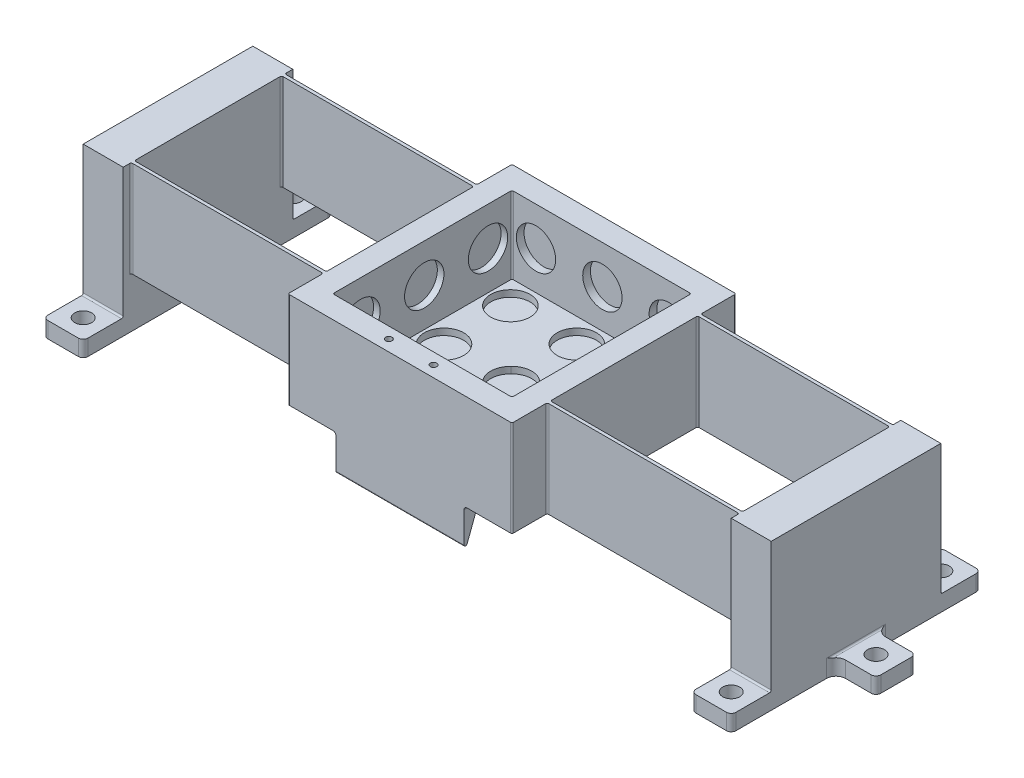
SolidWorks part; units mm, degrees
ref_plane "Front Plane" through (0, 0, 0) normal (0, 0, 1) x (1, 0, 0)
ref_plane "Top Plane" through (0, 0, 0) normal (0, 1, 0) x (1, 0, 0)
ref_plane "Right Plane" through (0, 0, 0) normal (1, 0, 0) x (0, 0, -1)
sketch "Sketch1" plane through (0, 0, 0) normal (0, 1, 0) x (1, 0, 0)
  line L1 (-35, -35) -> (35, -35)
  line L2 (-35, -35) -> (-35, 35)
  line L3 (-35, 35) -> (35, 35)
  line L4 (35, -35) -> (35, 35)
  line L5 (-35, -35) -> (35, 35) construction
  line L6 (-35, 35) -> (35, -35) construction
  point P0 (0, 0)
  dimension "D1" = 70
  dimension "D2" = 70
extrude "Boss-Extrude1" add sketch "Sketch1" along normal blind 30
shell "Shell1" thickness 7 removed face at (0, 30, 0)
sketch "Sketch2" plane through (0, 30, 0) normal (0, 1, 0) x (1, 0, 0)
  line L0 (-35, 35) -> (-35, -35) construction
  line L1 (-28, -28) -> (28, -28) construction
  line L2 (-28, -28) -> (-28, 28) construction
  line L3 (-28, 28) -> (28, 28) construction
  line L4 (28, -28) -> (28, 28) construction
  line L5 (-28, -28) -> (28, 28) construction
  line L6 (-28, 28) -> (28, -28) construction
  line L7 (35, 35) -> (-35, 35) construction
  point P0 (0, 0)
  dimension "D1" = 7
  dimension "D2" = 7
sketch "Sketch3" plane through (35, 0, 0) normal (1, 0, 0) x (0, 0, -1)
  line L0 (-35, 30) -> (35, 30) construction
  line L1 (-24, 30) -> (-23, 30)
  line L2 (-24, 30) -> (-24, 0)
  line L3 (-24, 0) -> (-23, 0)
  line L4 (-23, 30) -> (-23, 0)
  line L5 (-35, 0) -> (35, 0) construction
  line L11 (28, 30) -> (-28, 30) construction
  line L12 (24, 30) -> (23, 30)
  line L13 (24, 30) -> (24, 0)
  line L14 (24, 0) -> (23, 0)
  line L15 (23, 30) -> (23, 0)
  line L16 (-23.5, 30) -> (-23.5, 0) construction
  line L18 (23.5, 0) -> (23.5, 30) construction
  dimension "D1" = 23
  dimension "D2" = 1
  dimension "D3" = 23
extrude "Boss-Extrude2" add sketch "Sketch3" along normal blind 60
sketch "Sketch5" plane through (95, 0, 0) normal (1, 0, 0) x (0, 0, -1)
  line L0 (-24, 30) -> (-24, 0) construction
  line L1 (-26.5, 30) -> (26.5, 30)
  line L2 (-26.5, 30) -> (-26.5, 0)
  line L3 (-26.5, 0) -> (26.5, 0)
  line L4 (26.5, 30) -> (26.5, 0)
  line L5 (28, 30) -> (-28, 30) construction
  line L6 (24, 0) -> (35, 0) construction
  line L7 (24, 0) -> (24, 30) construction
  dimension "D1" = 2.5
  dimension "D2" = 2.5
extrude "Boss-Extrude3" add sketch "Sketch5" along normal blind 12.5
sketch "Sketch6" plane through (0, 0, 0) normal (0, -1, 0) x (1, 0, 0)
  line L1 (95, 26.5) -> (107.5, 26.5)
  line L2 (95, 26.5) -> (95, -26.5)
  line L3 (95, -26.5) -> (107.5, -26.5)
  line L4 (107.5, 26.5) -> (107.5, -26.5)
extrude "Boss-Extrude4" add sketch "Sketch6" along normal blind 15.75
sketch "Sketch8" plane through (0, -15.75, 0) normal (0, -1, 0) x (1, 0, 0)
  line L1 (107.5, -26.5) -> (95, -26.5)
  line L2 (107.5, -26.5) -> (107.5, -39)
  line L3 (107.5, -39) -> (95, -39)
  line L4 (95, -26.5) -> (95, -39)
  line L5 (107.5, 26.5) -> (95, 26.5)
  line L6 (107.5, 26.5) -> (107.5, 39)
  line L7 (107.5, 39) -> (95, 39)
  line L8 (95, 26.5) -> (95, 39)
  line L13 (107.5, -26.5) -> (107.5, 26.5) construction
  line L14 (120, -6.25) -> (107.5, -6.25)
  line L15 (120, -6.25) -> (120, 6.25)
  line L16 (120, 6.25) -> (107.5, 6.25)
  line L17 (107.5, -6.25) -> (107.5, 6.25)
  line L18 (120, -6.25) -> (107.5, 6.25) construction
  line L19 (120, 6.25) -> (107.5, -6.25) construction
  line L20 (107.5, 0) -> (120, 0) construction
  point P13 (113.75, 0)
  point P19 (107.5, 0)
  point P20 (107.5, 0)
extrude "Boss-Extrude5" add sketch "Sketch8" against normal blind 5
hole_wizard "Ø5.0mm Dowel Hole1" positions "Sketch9" profile "Sketch10" hole size "Ø5.0" standard "ANSI Metric"
sketch "Sketch9" plane through (0, -10.75, 0) normal (0, 1, 0) x (1, 0, 0)
  line L0 (101.25, 39) -> (101.25, 32.75) construction
  line L1 (95, 39) -> (107.5, 39) construction
  line L2 (101.25, 32.75) -> (107.5, 32.75) construction
  line L3 (107.5, 39) -> (107.5, 26.5) construction
  line L5 (107.5, 0) -> (113.75, 0) construction
  line L6 (107.5, -6.25) -> (107.5, 6.25) construction
  line L7 (113.75, 0) -> (113.75, 6.25) construction
  line L8 (107.5, 6.25) -> (120, 6.25) construction
  line L10 (101.25, -26.5) -> (101.25, -32.75) construction
  line L11 (95, -26.5) -> (107.5, -26.5) construction
  line L12 (101.25, -32.75) -> (107.5, -32.75) construction
  line L13 (107.5, -26.5) -> (107.5, -39) construction
  point P0 (101.25, 32.75)
  point P2 (113.75, 0)
  point P4 (101.25, -32.75)
sketch "Sketch10" plane through (101.25, -10.75, -32.75) normal (1, 0, 0) x (0, 0, 1)
  line L0 (0, 0) -> (0, 18.1023)
  line L1 (0, 18.1023) -> (2.65, 16.51)
  line L2 (2.65, 16.51) -> (2.65, 0)
  line L5 (2.65, 0) -> (0, 0)
  line L10 (0, 18.1023) -> (-2.65, 16.51) construction
  line L11 (0, -6.35) -> (0, 107.95) construction
  dimension "Hole Dia." = 5.3
  dimension "Hole Depth" = 16.51
  dimension "Drill Angle" = 118
mirror "Mirror1" about plane through (0, 0, 0) normal (1, 0, 0) of "Boss-Extrude2", "Boss-Extrude3", "Boss-Extrude5", "Boss-Extrude4", "Ø5.0mm Dowel Hole1"
fillet "Fillet1" radius 0.5 20 edges at (101.25, -10.75, 26.5) (-95, 15, 24) (-95, 15, 23) (-35, 15, 24) (-35, 15, 23) (-95, 15, -24) (-95, 15, -23) (-35, 15, -24) (-35, 15, -23) (-101.25, -10.75, -26.5) (-101.25, -10.75, 26.5) (35, 15, 24) (35, 15, 23) (95, 15, 24) (95, 15, 23) (35, 15, -24) (35, 15, -23) (95, 15, -24) (95, 15, -23) (101.25, -10.75, -26.5)
fillet "Fillet2" radius 1.5 12 edges at (120, -13.25, 6.25) (120, -13.25, -6.25) (107.5, -13.25, -39) (95, -13.25, -39) (107.5, -13.25, 39) (95, -13.25, 39) (-95, -13.25, -39) (-107.5, -13.25, -39) (-120, -13.25, -6.25) (-120, -13.25, 6.25) (-95, -13.25, 39) (-107.5, -13.25, 39)
sketch "Sketch11" plane through (0, 6, 0) normal (0, 1, 0) x (1, 0, 0)
  line L26 (-28, -28) -> (-28, 28) construction
  line L32 (-28, -28) -> (28, -28) construction
  circle A0 centre (-21, -21) radius 6.15
  dimension "D1" = 12.3
  dimension "D2" = 0.85
  dimension "D3" = 0.85
extrude "Cut-Extrude1" cut sketch "Sketch11" against normal blind 2.05
pattern_linear "LPattern1" count 3 spacing 20.75 along (1, 0, 0) count 3 spacing 20.75 along (0, 0, -1) of "Cut-Extrude1"
sketch "Sketch14" plane through (0, 6, 0) normal (0, 1, 0) x (1, 0, 0)
  line L0 (-28, 0) -> (0, 0) construction
  line L1 (-28, 28) -> (-28, -28) construction
  line L2 (0, 0) -> (0, -28) construction
  line L3 (-28, -28) -> (28, -28) construction
  circle A0 centre (0, 0) radius 6.15
  dimension "D1" = 12.3
extrude "Cut-Extrude4" cut sketch "Sketch14" against normal blind 2.05
sketch "Sketch12" plane through (-28, 0, 0) normal (1, 0, 0) x (0, 0, -1)
  line L5 (-28, 18) -> (-19.35, 18) construction
  line L6 (-28, 30) -> (-28, 6) construction
  circle A0 centre (-19.35, 18) radius 6.15
  dimension "D1" = 12.3
  dimension "D2" = 2.5
extrude "Cut-Extrude2" cut sketch "Sketch12" against normal blind 2.05
pattern_linear "LPattern2" count 3 spacing 19.925 along (0, 0, -1) of "Cut-Extrude2"
sketch "Sketch13" plane through (0, 0, -28) normal (0, 0, -1) x (-1, 0, 0)
  line L6 (-28, 30) -> (-28, 6) construction
  line L7 (-21, 18) -> (-28, 18) construction
  circle A0 centre (-21, 18) radius 6.15
  dimension "D1" = 12.3
  dimension "D3" = 0.85
extrude "Cut-Extrude3" cut sketch "Sketch13" along normal blind 2.4
pattern_linear "LPattern3" count 3 spacing 20.75 along (-1, 0, 0) of "Cut-Extrude3"
mirror "Mirror2" about plane through (0, 0, 0) normal (1, 0, 0) of "LPattern2", "Cut-Extrude2"
fillet "Fillet3" radius 0.5 4 edges at (28, 18, -28) (-28, 18, -28) (28, 18, 28) (-28, 18, 28)
fillet "Fillet4" radius 0.5 4 edges at (-35, 15, 35) (35, 15, 35) (-35, 15, -35) (35, 15, -35)
sketch "Sketch19" plane through (0, 0, 0) normal (1, 0, 0) x (0, 0, -1)
  line L0 (-30, 0) -> (-35, -13.25)
  line L1 (-35, -13.25) -> (-35, 0)
  line L2 (-35, 0) -> (-30, 0)
  line L3 (0, 0) -> (-30, 0) construction
  line L4 (37.5, -15.75) -> (-37.5, -15.75) construction
  dimension "D1" = 5
  dimension "D2" = 30
  dimension "D3" = 2.5
extrude "Boss-Extrude8" add sketch "Sketch19" along normal mid plane 40
sketch "Sketch20" plane through (0, 0, 0) normal (1, 0, 0) x (0, 0, -1)
  line L0 (-35, 20) -> (-42.5, 20)
  line L1 (-42.5, 20) -> (-42.5, 30)
  line L2 (-26.5, 30) -> (-42.5, 30) construction
  line L5 (-42.5, 30) -> (-40, 30)
  line L6 (-40, 30) -> (-40, 22.5)
  line L7 (-40, 22.5) -> (-35, 22.5)
  line L8 (-35, 22.5) -> (-35, 20)
  line L9 (-35, 30) -> (-35, 0) construction
  line L10 (-35, 0) -> (-35, 30) construction
  dimension "D1" = 5
  dimension "D2" = 10
  dimension "D3" = 2.5
  dimension "D4" = 2.5
extrude "Place For Sensor" [suppressed] add sketch "Sketch20" along normal mid plane 10
fillet "Place For Sensor Fillet5" [suppressed] radius 0.5
fillet "Place For Sensor Fillet6" [suppressed] radius 1.5
hole_wizard "Place For Sensor Ø3.0mm Dowel Hole2" [suppressed] positions "Sketch21" profile "Sketch22" hole size "Ø3.0" standard "ANSI Metric"
sketch "Sketch21" [suppressed] plane through (0, 0, 32.5) normal (0, 0, 1) x (1, 0, 0)
  line L0 (-2.5, 27.5) -> (2.5, 27.5) construction
  line L2 (-18, 30) -> (18, 30) construction
  line L3 (-5, 28.5) -> (-5, 20.5) construction
  line L4 (5, 28.5) -> (5, 20.5) construction
  point P0 (-2.5, 27.5)
  point P2 (2.5, 27.5)
  dimension "D1" = 2.5
  dimension "D2" = 2.5
  dimension "D3" = 2.5
sketch "Sketch22" plane through (-2.5, 27.5, 32.5) normal (1, 0, 0) x (0, -1, 0)
  line L0 (0, 0) -> (0, 2.5)
  line L1 (0, 2.5) -> (1.65, 2.5)
  line L2 (1.65, 2.5) -> (1.65, 0)
  line L5 (1.65, 0) -> (0, 0)
  line L11 (0, -6.35) -> (0, 107.95) construction
  dimension "Thru Hole Dia." = 3.3
  dimension "Thru Hole Depth" = 2.5
sketch "Sketch23" plane through (0, 30, 0) normal (0, 1, 0) x (1, 0, 0)
  line L1 (-28, -28) -> (28, -28) construction
  circle A0 centre (-7, -31.5) radius 1
  circle A1 centre (7, -31.5) radius 1
  dimension "D4" = 2
  dimension "D1" = 3.5
  dimension "D2" = 14
  dimension "D3" = 7
extrude "Cut-Extrude5" cut sketch "Sketch23" against normal blind 6
fillet "Fillet5" radius 0.5 1 edges at (0, -13.25, 35)
fillet "Fillet6" radius 1 3 edges at (-20, 0, 32.5) (20, 0, 32.5) (0, 0, 30)
fillet "Fillet8" radius 3 4 edges at (107.5, -13, 6.25) (107.5, -13, -6.25) (-107.5, -13, -6.25) (-107.5, -13, 6.25)
